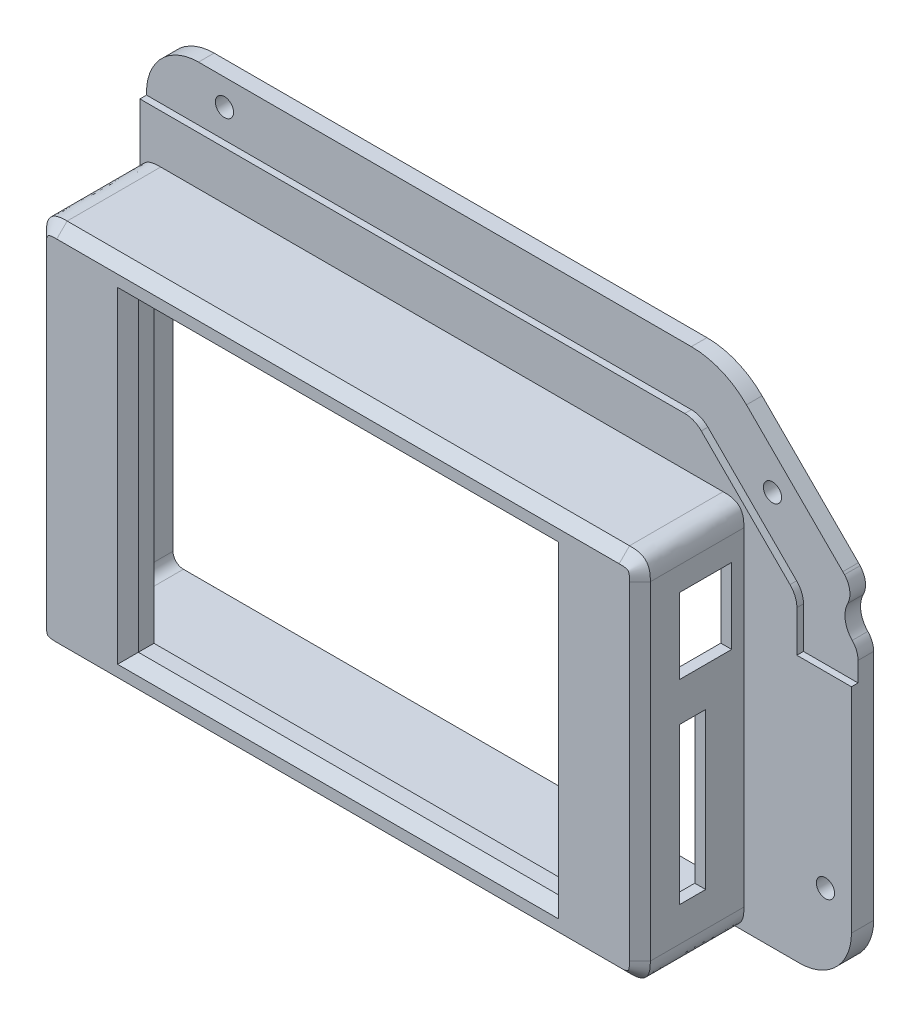
SolidWorks part; units mm, degrees
material "ABS"
ref_plane "Front Plane" through (0, 0, 0) normal (0, 0, 1) x (1, 0, 0)
ref_plane "Top Plane" through (0, 0, 0) normal (0, 1, 0) x (1, 0, 0)
ref_plane "Right Plane" through (0, 0, 0) normal (1, 0, 0) x (0, 0, -1)
sketch "Sketch1" plane through (0, 0, 0) normal (0, 0, 1) x (1, 0, 0)
  line L0 (56, 25) -> (58.1, 25)
  line L1 (58.1, 25) -> (58.1, -5)
  line L2 (58.1, -5) -> (56, -5)
  line L3 (56, -5) -> (56, 25)
  line L4 (56, -12.5) -> (58.1, -12.5)
  line L5 (58.1, -12.5) -> (58.1, -27)
  line L6 (58.1, -27) -> (56, -27)
  line L7 (56, -27) -> (56, -12.5)
  line L8 (47.6, -33.5) -> (54, -33.5)
  line L9 (56, -31.5) -> (56, -25.1)
  line L10 (56, -25.1) -> (51, -25.1)
  line L11 (47.6, -28.5) -> (47.6, -33.5)
  line L12 (56, 25.1) -> (56, 31.5)
  line L13 (54, 33.5) -> (47.6, 33.5)
  line L14 (47.6, 33.5) -> (47.6, 28.5)
  line L15 (51, 25.1) -> (56, 25.1)
  line L16 (-47.6, 33.5) -> (-54, 33.5)
  line L17 (-56, 31.5) -> (-56, 25.1)
  line L18 (-56, 25.1) -> (-51, 25.1)
  line L19 (-47.6, 28.5) -> (-47.6, 33.5)
  line L20 (-56, -25.1) -> (-56, -31.5)
  line L21 (-54, -33.5) -> (-47.6, -33.5)
  line L22 (-47.6, -33.5) -> (-47.6, -28.5)
  line L23 (-51, -25.1) -> (-56, -25.1)
  line L24 (58.1, -31.6) -> (58.1, 31.6)
  line L25 (54.1, 35.6) -> (-54.1, 35.6)
  line L26 (-58.1, 31.6) -> (-58.1, -31.6)
  line L27 (-54.1, -35.6) -> (54.1, -35.6)
  line L28 (42.5, -31.5) -> (42.5, 31.5)
  line L29 (42.5, 31.5) -> (-42.5, 31.5)
  line L30 (-42.5, 31.5) -> (-42.5, -31.5)
  line L31 (-42.5, -31.5) -> (42.5, -31.5)
  line L32 (40.4, 29.4) -> (-40.4, 29.4)
  line L33 (-40.4, 29.4) -> (-40.4, -29.4)
  line L34 (-40.4, -29.4) -> (40.4, -29.4)
  line L35 (40.4, -29.4) -> (40.4, 29.4)
  line L36 (-40.4, 0) -> (40.4, 0) construction
  line L37 (0, 29.4) -> (0, -29.4) construction
  line L38 (47.6, 33.5) -> (-47.6, 33.5)
  line L39 (-56, 25.1) -> (-56, -25.1)
  line L40 (-47.6, -33.5) -> (47.6, -33.5)
  line L41 (56, -12.5) -> (56, -5)
  arc A0 (54, -33.5) -> (56, -31.5) centre (54, -31.5) ccw
  arc A1 (51, -25.1) -> (47.6, -28.5) centre (51, -28.5) ccw
  arc A2 (56, 31.5) -> (54, 33.5) centre (54, 31.5) ccw
  arc A3 (47.6, 28.5) -> (51, 25.1) centre (51, 28.5) ccw
  arc A4 (-54, 33.5) -> (-56, 31.5) centre (-54, 31.5) ccw
  arc A5 (-51, 25.1) -> (-47.6, 28.5) centre (-51, 28.5) ccw
  arc A6 (-56, -31.5) -> (-54, -33.5) centre (-54, -31.5) ccw
  arc A7 (-47.6, -28.5) -> (-51, -25.1) centre (-51, -28.5) ccw
  circle A8 centre (51, 28.5) radius 1.3
  circle A9 centre (-51, 28.5) radius 1.3
  circle A10 centre (-51, -28.5) radius 1.3
  circle A11 centre (51, -28.5) radius 1.3
  spline S0 degree 5 poles (54.1, -35.6) (54.7728, -35.6) (55.4456, -35.6) (56.9284, -35.3132) (57.8132, -34.4284) (58.1, -32.9456) (58.1, -32.2728) (58.1, -31.6) knots 0 0 0 0 0 0 0.5 0.5 1 1 1 1 1 1
  spline S1 degree 5 poles (58.1, 31.6) (58.1, 32.2728) (58.1, 32.9456) (57.8132, 34.4284) (56.9284, 35.3132) (55.4456, 35.6) (54.7728, 35.6) (54.1, 35.6) knots 0 0 0 0 0 0 0.5 0.5 1 1 1 1 1 1
  spline S2 degree 5 poles (-54.1, 35.6) (-54.7728, 35.6) (-55.4456, 35.6) (-56.9284, 35.3132) (-57.8132, 34.4284) (-58.1, 32.9456) (-58.1, 32.2728) (-58.1, 31.6) knots 0 0 0 0 0 0 0.5 0.5 1 1 1 1 1 1
  spline S3 degree 5 poles (-58.1, -31.6) (-58.1, -32.2728) (-58.1, -32.9456) (-57.8132, -34.4284) (-56.9284, -35.3132) (-55.4456, -35.6) (-54.7728, -35.6) (-54.1, -35.6) knots 0 0 0 0 0 0 0.5 0.5 1 1 1 1 1 1
sketch "Sketch2" plane through (0, 0, 0) normal (0, 0, 1) x (1, 0, 0)
  line L0 (98.7914, 85.4501) -> (98.7914, -409.5499)
  line L1 (95.3675, 85.4501) -> (95.3675, -409.5499)
  line L2 (-376.1657, 85.4501) -> (93.7486, 85.4501)
  line L3 (-376.1657, 82.0262) -> (93.7486, 82.0262)
  line L4 (95.3675, 85.4501) -> (73.7914, 85.4501)
  line L5 (-329.1375, 45.4501) -> (46.7203, 45.4501)
  line L6 (50.2559, 43.9857) -> (67.3269, 26.9146)
  line L7 (68.7914, 80.4501) -> (68.7914, -404.5499)
  arc A0 (73.7914, 85.4501) -> (68.7914, 80.4501) centre (73.7914, 80.4501) ccw
  circle A1 centre (61.1725, 65.1501) radius 2.75
  circle A2 centre (81.27, 75.4501) radius 2.5
  circle A3 centre (81.27, 50.4501) radius 2.5
  circle A4 centre (81.27, 25.4501) radius 2.5
  arc A5 (50.2559, 43.9857) -> (46.7203, 45.4501) centre (46.7203, 40.4501) ccw
  arc A6 (68.7914, 23.3791) -> (67.3269, 26.9146) centre (63.7914, 23.3791) ccw
sketch "Sketch3" plane through (0, 0, 0) normal (0, 0, 1) x (1, 0, 0)
  line L0 (-47.6, -33.5) -> (47.6, -33.5) construction
  line L1 (-56, -25.1) -> (-56, -31.5) construction
  line L2 (-56, 25.1) -> (-56, -25.1) construction
  line L3 (-58.1, 31.6) -> (-58.1, -31.6) construction
  line L4 (-54.1, -35.6) -> (54.1, -35.6) construction
  line L5 (-47.6, -33.5) -> (54, -33.5)
  line L6 (-56, -25.1) -> (-56, -31.5)
  line L7 (-56, 31.5) -> (-56, -25.1)
  line L8 (-58.1, 45.4501) -> (-58.1, -31.6)
  line L9 (-54.1, -35.6) -> (68.7914, -35.6)
  line L12 (78.7914, 80.4501) -> (78.7914, -404.5499)
  line L13 (78.7914, 25.4501) -> (78.7914, -25.6)
  line L16 (78.7914, 15.4501) -> (58.1, 15.4501) construction
  line L17 (58.1, 25) -> (58.1, -5) construction
  line L18 (57.3269, 51.0567) -> (74.398, 33.9857)
  line L19 (-329.1375, 55.4501) -> (46.7203, 55.4501)
  line L20 (57.3269, 51.0567) -> (75.8625, 32.5212)
  line L21 (-48.1, 55.4501) -> (46.7203, 55.4501)
  line L22 (-376.1657, 85.4501) -> (93.7486, 85.4501) construction
  line L23 (78.7914, 14.9501) -> (58.1, 14.9501)
  line L28 (56, -31.5) -> (56, -25.1) construction
  line L29 (56, -27) -> (56, -12.5) construction
  line L30 (56, -12.5) -> (56, -5) construction
  line L31 (56, -5) -> (56, 25) construction
  line L32 (56, 25.1) -> (56, 31.5) construction
  line L33 (54, 33.5) -> (47.6, 33.5) construction
  line L34 (47.6, 33.5) -> (-47.6, 33.5) construction
  line L35 (-47.6, 33.5) -> (-54, 33.5) construction
  line L36 (56, -31.5) -> (56, -25.1)
  line L37 (56, -27) -> (56, -12.5)
  line L38 (56, -12.5) -> (56, -5)
  line L39 (56, -5) -> (56, 25)
  line L40 (56, 25.1) -> (56, 31.5)
  line L41 (54, 33.5) -> (47.6, 33.5)
  line L42 (47.6, 33.5) -> (-47.6, 33.5)
  line L43 (-47.6, 33.5) -> (-54, 33.5)
  line L44 (58.1, -31.6) -> (58.1, 31.6) construction
  line L45 (54.1, 35.6) -> (-54.1, 35.6) construction
  line L46 (58.1, -31.6) -> (58.1, 31.6)
  line L47 (54.1, 35.6) -> (-54.1, 35.6)
  arc A0 (-56, -31.5) -> (-54, -33.5) centre (-54, -31.5) ccw construction
  arc A1 (-56, -31.5) -> (-54, -33.5) centre (-54, -31.5) ccw
  arc A2 (68.7914, -35.6) -> (78.7914, -25.6) centre (68.7914, -25.6) ccw
  arc A5 (57.3269, 51.0567) -> (46.7203, 55.4501) centre (46.7203, 40.4501) ccw
  arc A6 (57.3269, 51.0567) -> (46.7203, 55.4501) centre (46.7203, 40.4501) ccw
  arc A8 (75.8625, 32.5212) -> (78.7914, 25.4501) centre (68.7914, 25.4501) cw
  arc A9 (54, -33.5) -> (56, -31.5) centre (54, -31.5) ccw construction
  arc A10 (56, 31.5) -> (54, 33.5) centre (54, 31.5) ccw construction
  arc A11 (-54, 33.5) -> (-56, 31.5) centre (-54, 31.5) ccw construction
  arc A12 (54, -33.5) -> (56, -31.5) centre (54, -31.5) ccw
  arc A13 (56, 31.5) -> (54, 33.5) centre (54, 31.5) ccw
  arc A14 (-54, 33.5) -> (-56, 31.5) centre (-54, 31.5) ccw
  arc A15 (-58.1, 45.4501) -> (-48.1, 55.4501) centre (-48.1, 45.4501) cw
  spline S0 degree 5 poles (-451.1974, 887.8948) (-47.5589, -137.72) (-52.7107, -16.9947) (-63.1302, -36.2248) (-58.7249, -40.6302) (-39.4949, -30.2108) (-160.2167, -25.059) (865.3606, -428.6839) knots -1.989435 -1.989435 -1.989435 -1.989435 -1.989435 -1.989435 0.5 0.5 2.989419 2.989419 2.989419 2.989419 2.989419 2.989419 only from (-58.1, -31.6) to (-54.1, -35.6) construction
  spline S1 degree 5 poles (-58.1, -31.6) (-58.1, -32.2728) (-58.1, -32.9456) (-57.8132, -34.4284) (-56.9284, -35.3132) (-55.4456, -35.6) (-54.7728, -35.6) (-54.1, -35.6) knots 0 0 0 0 0 0 0.5 0.5 1 1 1 1 1 1
  spline S2 degree 5 poles (-865.3948, -428.6974) (160.22, -25.0589) (39.4947, -30.2107) (58.7248, -40.6302) (63.1302, -36.2249) (52.7108, -16.9949) (47.559, -137.7167) (451.1839, 887.8606) knots -1.989435 -1.989435 -1.989435 -1.989435 -1.989435 -1.989435 0.5 0.5 2.989419 2.989419 2.989419 2.989419 2.989419 2.989419 only from (54.1, -35.6) to (58.1, -31.6) construction
  spline S3 degree 5 poles (451.1974, -887.8948) (47.5589, 137.72) (52.7107, 16.9947) (63.1302, 36.2248) (58.7249, 40.6302) (39.4949, 30.2108) (160.2167, 25.059) (-865.3606, 428.6839) knots -1.989435 -1.989435 -1.989435 -1.989435 -1.989435 -1.989435 0.5 0.5 2.989419 2.989419 2.989419 2.989419 2.989419 2.989419 only from (58.1, 31.6) to (54.1, 35.6) construction
  spline S4 degree 5 poles (865.3948, 428.6974) (-160.22, 25.0589) (-39.4947, 30.2107) (-58.7248, 40.6302) (-63.1302, 36.2249) (-52.7108, 16.9949) (-47.559, 137.7167) (-451.1839, -887.8606) knots -1.989435 -1.989435 -1.989435 -1.989435 -1.989435 -1.989435 0.5 0.5 2.989419 2.989419 2.989419 2.989419 2.989419 2.989419 only from (-54.1, 35.6) to (-58.1, 31.6) construction
  spline S5 degree 5 poles (54.1, -35.6) (54.7728, -35.6) (55.4456, -35.6) (56.9284, -35.3132) (57.8132, -34.4284) (58.1, -32.9456) (58.1, -32.2728) (58.1, -31.6) knots 0 0 0 0 0 0 0.5 0.5 1 1 1 1 1 1
  spline S6 degree 5 poles (58.1, 31.6) (58.1, 32.2728) (58.1, 32.9456) (57.8132, 34.4284) (56.9284, 35.3132) (55.4456, 35.6) (54.7728, 35.6) (54.1, 35.6) knots 0 0 0 0 0 0 0.5 0.5 1 1 1 1 1 1
  spline S7 degree 5 poles (-54.1, 35.6) (-54.7728, 35.6) (-55.4456, 35.6) (-56.9284, 35.3132) (-57.8132, 34.4284) (-58.1, 32.9456) (-58.1, 32.2728) (-58.1, 31.6) knots 0 0 0 0 0 0 0.5 0.5 1 1 1 1 1 1
  dimension "D5" = 10
  dimension "D6" = 10
  dimension "D7" = 10
  dimension "D3" = 70
  dimension "D1" = 10
  dimension "D2" = 10
  dimension "D4" = 0.5
extrude "Boss-Extrude1" add sketch "Sketch3" against normal blind 4.27 contours L21 A6 L20 A8 L13 A2 L9 S1 L8 A15
extrude "Cut-Extrude1" cut sketch "Sketch3<4>" against normal blind 1.27 contours L16 L13 A8 L20 A6 L21 A15 L8 S7 L47 S6 L46 region at (12.237, 42.2848, 0)
sketch "Sketch3<4>" plane through (0, 0, 0) normal (0, 0, 1) x (1, 0, 0) same geometry as "Sketch3"
sketch "Sketch4" plane through (0, 0, 0) normal (0, 0, 1) x (1, 0, 0)
  line L0 (-56, -31.5) -> (-56, 31.5)
  line L1 (-54, 33.5) -> (54, 33.5)
  line L2 (56, 31.5) -> (56, -31.5)
  line L3 (54, -33.5) -> (-54, -33.5)
  arc A0 (-56, -31.5) -> (-54, -33.5) centre (-54, -31.5) ccw construction
  arc A1 (54, -33.5) -> (56, -31.5) centre (54, -31.5) ccw construction
  arc A2 (56, 31.5) -> (54, 33.5) centre (54, 31.5) ccw construction
  arc A3 (-54, 33.5) -> (-56, 31.5) centre (-54, 31.5) ccw construction
  arc A4 (-56, -31.5) -> (-54, -33.5) centre (-54, -31.5) ccw
  arc A5 (54, -33.5) -> (56, -31.5) centre (54, -31.5) ccw
  arc A6 (56, 31.5) -> (54, 33.5) centre (54, 31.5) ccw
  arc A7 (-54, 33.5) -> (-56, 31.5) centre (-54, 31.5) ccw
extrude "Cut-Extrude2" cut sketch "Sketch4" against normal through all
sketch "Sketch5" plane through (0, 0, 0) normal (0, 0, 1) x (1, 0, 0)
  line L0 (54.1, -35.6) -> (-54.1, -35.6)
  line L1 (-58.1, -31.6) -> (-58.1, 31.6)
  line L2 (-54.1, 35.6) -> (54.1, 35.6)
  line L3 (58.1, 31.6) -> (58.1, -31.6)
  line L4 (56, -31.5) -> (56, 31.5) construction
  line L5 (-54, -33.5) -> (54, -33.5) construction
  line L6 (-56, 31.5) -> (-56, -31.5) construction
  line L7 (54, 33.5) -> (-54, 33.5) construction
  line L8 (56, -31.5) -> (56, 31.5)
  line L9 (-54, -33.5) -> (54, -33.5)
  line L10 (-56, 31.5) -> (-56, -31.5)
  line L11 (54, 33.5) -> (-54, 33.5)
  arc A0 (56, 31.5) -> (54, 33.5) centre (54, 31.5) ccw construction
  arc A1 (54, -33.5) -> (56, -31.5) centre (54, -31.5) ccw construction
  arc A2 (-56, -31.5) -> (-54, -33.5) centre (-54, -31.5) ccw construction
  arc A3 (-54, 33.5) -> (-56, 31.5) centre (-54, 31.5) ccw construction
  arc A4 (56, 31.5) -> (54, 33.5) centre (54, 31.5) ccw
  arc A5 (54, -33.5) -> (56, -31.5) centre (54, -31.5) ccw
  arc A6 (-56, -31.5) -> (-54, -33.5) centre (-54, -31.5) ccw
  arc A7 (-54, 33.5) -> (-56, 31.5) centre (-54, 31.5) ccw
  spline S0 degree 5 poles (-1799.305, -785.9818) (240.9375, -22.324) (35.4019, -27.9004) (59.4949, -41.9944) (64.4944, -36.995) (50.4005, -12.9021) (44.8241, -218.4331) (808.4613, 1821.7503) knots -2.325198 -2.325198 -2.325198 -2.325198 -2.325198 -2.325198 0.5 0.5 3.325183 3.325183 3.325183 3.325183 3.325183 3.325183 only from (54.1, -35.6) to (58.1, -31.6) construction
  spline S1 degree 5 poles (-808.4818, 1821.805) (-44.824, -218.4375) (-50.4004, -12.9019) (-64.4944, -36.9949) (-59.495, -41.9944) (-35.4021, -27.9005) (-240.9331, -22.3241) (1799.2503, -785.9613) knots -2.325198 -2.325198 -2.325198 -2.325198 -2.325198 -2.325198 0.5 0.5 3.325183 3.325183 3.325183 3.325183 3.325183 3.325183 only from (-58.1, -31.6) to (-54.1, -35.6) construction
  spline S2 degree 5 poles (1799.305, 785.9818) (-240.9375, 22.324) (-35.4019, 27.9004) (-59.4949, 41.9944) (-64.4944, 36.995) (-50.4005, 12.9021) (-44.8241, 218.4331) (-808.4613, -1821.7503) knots -2.325198 -2.325198 -2.325198 -2.325198 -2.325198 -2.325198 0.5 0.5 3.325183 3.325183 3.325183 3.325183 3.325183 3.325183 only from (-54.1, 35.6) to (-58.1, 31.6) construction
  spline S3 degree 5 poles (808.4818, -1821.805) (44.824, 218.4375) (50.4004, 12.9019) (64.4944, 36.9949) (59.495, 41.9944) (35.4021, 27.9005) (240.9331, 22.3241) (-1799.2503, 785.9613) knots -2.325198 -2.325198 -2.325198 -2.325198 -2.325198 -2.325198 0.5 0.5 3.325183 3.325183 3.325183 3.325183 3.325183 3.325183 only from (58.1, 31.6) to (54.1, 35.6) construction
  spline S4 degree 5 poles (54.1, -35.6) (54.7728, -35.6) (55.4456, -35.6) (56.9284, -35.3132) (57.8132, -34.4284) (58.1, -32.9456) (58.1, -32.2728) (58.1, -31.6) knots 0 0 0 0 0 0 0.5 0.5 1 1 1 1 1 1
  spline S5 degree 5 poles (-58.1, -31.6) (-58.1, -32.2728) (-58.1, -32.9456) (-57.8132, -34.4284) (-56.9284, -35.3132) (-55.4456, -35.6) (-54.7728, -35.6) (-54.1, -35.6) knots 0 0 0 0 0 0 0.5 0.5 1 1 1 1 1 1
  spline S6 degree 5 poles (-54.1, 35.6) (-54.7728, 35.6) (-55.4456, 35.6) (-56.9284, 35.3132) (-57.8132, 34.4284) (-58.1, 32.9456) (-58.1, 32.2728) (-58.1, 31.6) knots 0 0 0 0 0 0 0.5 0.5 1 1 1 1 1 1
  spline S7 degree 5 poles (58.1, 31.6) (58.1, 32.2728) (58.1, 32.9456) (57.8132, 34.4284) (56.9284, 35.3132) (55.4456, 35.6) (54.7728, 35.6) (54.1, 35.6) knots 0 0 0 0 0 0 0.5 0.5 1 1 1 1 1 1
extrude "Boss-Extrude2" add sketch "Sketch5" along normal blind 18
sketch "Sketch6" plane through (0, 0, 18) normal (0, 0, 1) x (1, 0, 0)
  line L0 (-40.4, 29.4) -> (-40.4, -29.4) construction
  line L1 (-40.4, -29.4) -> (40.4, -29.4) construction
  line L2 (40.4, -29.4) -> (40.4, 29.4) construction
  line L3 (40.4, 29.4) -> (-40.4, 29.4) construction
  line L4 (58.1, -31.6) -> (58.1, 31.6)
  line L5 (54.1, 35.6) -> (-54.1, 35.6)
  line L6 (-58.1, 31.6) -> (-58.1, -31.6)
  line L7 (-54.1, -35.6) -> (54.1, -35.6)
  line L8 (58.1, -31.6) -> (58.1, 31.6)
  line L9 (54.1, 35.6) -> (-54.1, 35.6)
  line L10 (-58.1, 31.6) -> (-58.1, -31.6)
  line L11 (-54.1, -35.6) -> (54.1, -35.6)
  line L12 (-40.4, 29.4) -> (-40.4, -29.4)
  line L13 (-40.4, -29.4) -> (40.4, -29.4)
  line L14 (40.4, -29.4) -> (40.4, 29.4)
  line L15 (40.4, 29.4) -> (-40.4, 29.4)
  spline S4 degree 5 poles (-2737.4679, -1132.0779) (312.9698, -20.6591) (32.5131, -26.1748) (60.0701, -42.9574) (65.4574, -37.5702) (48.6749, -10.0133) (43.1592, -290.4662) (1154.5598, 2759.9182) knots -2.544295 -2.544295 -2.544295 -2.544295 -2.544295 -2.544295 0.5 0.5 3.544285 3.544285 3.544285 3.544285 3.544285 3.544285 only from (54.1, -35.6) to (58.1, -31.6)
  spline S5 degree 5 poles (1154.5779, -2759.9679) (43.1591, 290.4698) (48.6748, 10.0131) (65.4574, 37.5701) (60.0702, 42.9574) (32.5133, 26.1749) (312.9662, 20.6592) (-2737.4182, 1132.0598) knots -2.544295 -2.544295 -2.544295 -2.544295 -2.544295 -2.544295 0.5 0.5 3.544285 3.544285 3.544285 3.544285 3.544285 3.544285 only from (58.1, 31.6) to (54.1, 35.6)
  spline S6 degree 5 poles (2737.4679, 1132.0779) (-312.9698, 20.6591) (-32.5131, 26.1748) (-60.0701, 42.9574) (-65.4574, 37.5702) (-48.6749, 10.0133) (-43.1592, 290.4662) (-1154.5598, -2759.9182) knots -2.544295 -2.544295 -2.544295 -2.544295 -2.544295 -2.544295 0.5 0.5 3.544285 3.544285 3.544285 3.544285 3.544285 3.544285 only from (-54.1, 35.6) to (-58.1, 31.6)
  spline S7 degree 5 poles (-1154.5779, 2759.9679) (-43.1591, -290.4698) (-48.6748, -10.0131) (-65.4574, -37.5701) (-60.0702, -42.9574) (-32.5133, -26.1749) (-312.9662, -20.6592) (2737.4182, -1132.0598) knots -2.544295 -2.544295 -2.544295 -2.544295 -2.544295 -2.544295 0.5 0.5 3.544285 3.544285 3.544285 3.544285 3.544285 3.544285 only from (-58.1, -31.6) to (-54.1, -35.6)
  spline S8 degree 5 poles (54.1, -35.6) (54.7728, -35.6) (55.4456, -35.6) (56.9284, -35.3132) (57.8132, -34.4284) (58.1, -32.9456) (58.1, -32.2728) (58.1, -31.6) knots 0 0 0 0 0 0 0.5 0.5 1 1 1 1 1 1
  spline S9 degree 5 poles (58.1, 31.6) (58.1, 32.2728) (58.1, 32.9456) (57.8132, 34.4284) (56.9284, 35.3132) (55.4456, 35.6) (54.7728, 35.6) (54.1, 35.6) knots 0 0 0 0 0 0 0.5 0.5 1 1 1 1 1 1
  spline S10 degree 5 poles (-54.1, 35.6) (-54.7728, 35.6) (-55.4456, 35.6) (-56.9284, 35.3132) (-57.8132, 34.4284) (-58.1, 32.9456) (-58.1, 32.2728) (-58.1, 31.6) knots 0 0 0 0 0 0 0.5 0.5 1 1 1 1 1 1
  spline S11 degree 5 poles (-58.1, -31.6) (-58.1, -32.2728) (-58.1, -32.9456) (-57.8132, -34.4284) (-56.9284, -35.3132) (-55.4456, -35.6) (-54.7728, -35.6) (-54.1, -35.6) knots 0 0 0 0 0 0 0.5 0.5 1 1 1 1 1 1
  dimension "D1" = 0
extrude "Boss-Extrude3" add sketch "Sketch6" along normal blind 2
sketch "Sketch7" plane through (0, 0, 18) normal (0, 0, -1) x (-1, 0, 0)
  line L0 (-47.6, -33.5) -> (-54, -33.5) construction
  line L1 (-56, -31.5) -> (-56, -25.1) construction
  line L2 (-56, -25.1) -> (-51, -25.1) construction
  line L3 (-47.6, -28.5) -> (-47.6, -33.5) construction
  line L4 (56, -25.1) -> (56, -31.5) construction
  line L5 (54, -33.5) -> (47.6, -33.5) construction
  line L6 (47.6, -33.5) -> (47.6, -28.5) construction
  line L7 (51, -25.1) -> (56, -25.1) construction
  line L8 (47.6, 33.5) -> (54, 33.5) construction
  line L9 (56, 31.5) -> (56, 25.1) construction
  line L10 (56, 25.1) -> (51, 25.1) construction
  line L11 (47.6, 28.5) -> (47.6, 33.5) construction
  line L12 (-47.6, 33.5) -> (-47.6, 28.5) construction
  line L13 (-51, 25.1) -> (-56, 25.1) construction
  line L14 (-56, 25.1) -> (-56, 31.5) construction
  line L15 (-54, 33.5) -> (-47.6, 33.5) construction
  line L16 (-47.6, -33.5) -> (-54, -33.5)
  line L17 (-56, -31.5) -> (-56, -25.1)
  line L18 (-56, -25.1) -> (-51, -25.1)
  line L19 (-47.6, -28.5) -> (-47.6, -33.5)
  line L20 (56, -25.1) -> (56, -31.5)
  line L21 (54, -33.5) -> (47.6, -33.5)
  line L22 (47.6, -33.5) -> (47.6, -28.5)
  line L23 (51, -25.1) -> (56, -25.1)
  line L24 (47.6, 33.5) -> (54, 33.5)
  line L25 (56, 31.5) -> (56, 25.1)
  line L26 (56, 25.1) -> (51, 25.1)
  line L27 (47.6, 28.5) -> (47.6, 33.5)
  line L28 (-47.6, 33.5) -> (-47.6, 28.5)
  line L29 (-51, 25.1) -> (-56, 25.1)
  line L30 (-56, 25.1) -> (-56, 31.5)
  line L31 (-54, 33.5) -> (-47.6, 33.5)
  circle A0 centre (-51, -28.5) radius 1.3 construction
  circle A1 centre (51, -28.5) radius 1.3 construction
  circle A2 centre (51, 28.5) radius 1.3 construction
  circle A3 centre (-51, 28.5) radius 1.3 construction
  arc A4 (-47.6, -28.5) -> (-51, -25.1) centre (-51, -28.5) ccw construction
  arc A5 (-56, -31.5) -> (-54, -33.5) centre (-54, -31.5) ccw construction
  arc A6 (54, -33.5) -> (56, -31.5) centre (54, -31.5) ccw construction
  arc A7 (51, -25.1) -> (47.6, -28.5) centre (51, -28.5) ccw construction
  arc A8 (56, 31.5) -> (54, 33.5) centre (54, 31.5) ccw construction
  arc A9 (47.6, 28.5) -> (51, 25.1) centre (51, 28.5) ccw construction
  arc A10 (-51, 25.1) -> (-47.6, 28.5) centre (-51, 28.5) ccw construction
  arc A11 (-54, 33.5) -> (-56, 31.5) centre (-54, 31.5) ccw construction
  circle A12 centre (-51, -28.5) radius 1.3
  circle A13 centre (51, -28.5) radius 1.3
  circle A14 centre (51, 28.5) radius 1.3
  circle A15 centre (-51, 28.5) radius 1.3
  arc A16 (-47.6, -28.5) -> (-51, -25.1) centre (-51, -28.5) ccw
  arc A17 (-56, -31.5) -> (-54, -33.5) centre (-54, -31.5) ccw
  arc A18 (54, -33.5) -> (56, -31.5) centre (54, -31.5) ccw
  arc A19 (51, -25.1) -> (47.6, -28.5) centre (51, -28.5) ccw
  arc A20 (56, 31.5) -> (54, 33.5) centre (54, 31.5) ccw
  arc A21 (47.6, 28.5) -> (51, 25.1) centre (51, 28.5) ccw
  arc A22 (-51, 25.1) -> (-47.6, 28.5) centre (-51, 28.5) ccw
  arc A23 (-54, 33.5) -> (-56, 31.5) centre (-54, 31.5) ccw
extrude "Boss-Extrude4" add sketch "Sketch7" along normal blind 5
chamfer "Chamfer1" distance 2 angle 45 13 edges at (0, -33.5, 18) (47.6, -31, 18) (53.5, -25.1, 18) (48.5958, -26.0958, 18) (56, 0, 18) (53.5, 25.1, 18) (47.6, 31, 18) (48.5958, 26.0958, 18) (0, 33.5, 18) (-47.6, 31, 18) (-48.5958, 26.0958, 18) (-53.5, 25.1, 18) (-56, 0, 18)
sketch "Sketch8" plane through (0, 0, 18) normal (0, 0, -1) x (-1, 0, 0)
  line L0 (-47.6, 33.5) -> (47.6, 33.5) construction
  line L1 (-42.5, 33.5) -> (42.5, 33.5)
  line L2 (-42.5, 33.5) -> (-42.5, -33.5)
  line L3 (-42.5, -33.5) -> (42.5, -33.5)
  line L4 (42.5, 33.5) -> (42.5, -33.5)
  line L6 (47.6, -33.5) -> (-47.6, -33.5) construction
  line L7 (42.5, 31.5) -> (42.5, -31.5) construction
  line L8 (-42.5, -31.5) -> (-42.5, 31.5) construction
  line L9 (40.4, 29.4) -> (40.4, -29.4) construction
  line L10 (40.4, -29.4) -> (-40.4, -29.4) construction
  line L11 (-40.4, -29.4) -> (-40.4, 29.4) construction
  line L12 (-40.4, 29.4) -> (40.4, 29.4) construction
  line L13 (40.4, 29.4) -> (40.4, -29.4)
  line L14 (40.4, -29.4) -> (-40.4, -29.4)
  line L15 (-40.4, -29.4) -> (-40.4, 29.4)
  line L16 (-40.4, 29.4) -> (40.4, 29.4)
extrude "Boss-Extrude5" add sketch "Sketch8" along normal blind 3
chamfer "Chamfer2" distance 2 angle 45 12 edges at (40.4, 0, 20) (0, -29.4, 20) (-40.4, 0, 20) (0, 29.4, 20) (-57.1039, -34.8309, 20) (0, -35.6, 20) (-58.1, 0, 20) (57.3309, -34.6039, 20) (-57.3309, 34.6039, 20) (58.1, 0, 20) (0, 35.6, 20) (57.1039, 34.8309, 20)
sketch "Sketch9" plane through (56, 0, 0) normal (-1, 0, 0) x (0, 0, 1)
  line L0 (13, -25.1) -> (13, -31.5) construction
  line L1 (12.35, 12.5) -> (2.35, 12.5)
  line L2 (12.35, 12.5) -> (12.35, 27)
  line L3 (12.35, 27) -> (2.35, 27)
  line L4 (2.35, 12.5) -> (2.35, 27)
  line L5 (12.35, -25) -> (7.35, -25)
  line L6 (12.35, -25) -> (12.35, 5)
  line L7 (12.35, 5) -> (7.35, 5)
  line L8 (7.35, -25) -> (7.35, 5)
  line L9 (13, 31.5) -> (13, 25.1) construction
  line L10 (-1.27, 31.6) -> (18, 31.6) construction
  line L12 (18, -31.6) -> (0, -31.6) construction
  dimension "D1" = 10
  dimension "D2" = 0.65
  dimension "D3" = 0.65
  dimension "D4" = 5
  dimension "D5" = 6.6
  dimension "D6" = 30
  dimension "D7" = 14.5
  dimension "D8" = 4.6
extrude "Cut-Extrude3" cut sketch "Sketch9" against normal up to surface (2.1 mm away)
sketch "Sketch10" plane through (0, 0, -4.27) normal (0, 0, -1) x (-1, 0, 0)
  line L10 (-73.7914, 23.3791) -> (-73.7914, -34.2603) construction
  line L11 (48.1, 55.4501) -> (-46.7203, 55.4501) construction
  line L12 (329.1375, 50.4501) -> (-46.7203, 50.4501)
  line L13 (-53.7914, 47.5212) -> (-70.8625, 30.4501)
  line L14 (56.7603, 50.4501) -> (-46.7203, 50.4501) construction
  line L15 (-53.7914, 47.5212) -> (-70.8625, 30.4501) construction
  line L16 (-57.3269, 51.0567) -> (-75.8625, 32.5212) construction
  line L17 (-78.7914, 25.4501) -> (-78.7914, -25.6) construction
  line L18 (54.1, -35.6) -> (-68.7914, -35.6) construction
  line L19 (58.1, 45.4501) -> (58.1, -31.6) construction
  line L20 (48.1, 55.4501) -> (-46.7203, 55.4501)
  line L21 (-57.3269, 51.0567) -> (-75.8625, 32.5212)
  line L22 (-78.7914, 25.4501) -> (-78.7914, -25.6)
  line L23 (54.1, -35.6) -> (-68.7914, -35.6)
  line L24 (58.1, 45.4501) -> (58.1, -31.6)
  arc A8 (-78.7914, -25.6) -> (-68.7914, -35.6) centre (-68.7914, -25.6) ccw construction
  arc A10 (-70.8625, 30.4501) -> (-73.7914, 23.3791) centre (-63.7914, 23.3791) ccw
  arc A11 (-46.7203, 50.4501) -> (-53.7914, 47.5212) centre (-46.7203, 40.4501) ccw
  arc A12 (-70.8625, 30.4501) -> (-73.7914, 23.3791) centre (-63.7914, 23.3791) ccw construction
  arc A13 (-46.7203, 50.4501) -> (-53.7914, 47.5212) centre (-46.7203, 40.4501) ccw construction
  arc A14 (-46.7203, 55.4501) -> (-57.3269, 51.0567) centre (-46.7203, 40.4501) ccw construction
  arc A15 (-75.8625, 32.5212) -> (-78.7914, 25.4501) centre (-68.7914, 25.4501) ccw construction
  arc A16 (58.1, 45.4501) -> (48.1, 55.4501) centre (48.1, 45.4501) ccw construction
  arc A17 (-46.7203, 55.4501) -> (-57.3269, 51.0567) centre (-46.7203, 40.4501) ccw
  arc A18 (-75.8625, 32.5212) -> (-78.7914, 25.4501) centre (-68.7914, 25.4501) ccw
  arc A19 (-78.7914, -25.6) -> (-68.7914, -35.6) centre (-68.7914, -25.6) ccw
  circle A20 centre (43.1, 50.4501) radius 1.75
  circle A21 centre (-62.3269, 38.9857) radius 1.75
  circle A22 centre (-73.7914, -20.6) radius 1.75
  circle A23 centre (-81.27, 25.4501) radius 5
  spline S0 degree 5 poles (451.1974, 887.8948) (47.5589, -137.72) (52.7107, -16.9947) (63.1302, -36.2248) (58.7249, -40.6302) (39.4949, -30.2108) (160.2167, -25.059) (-865.3606, -428.6839) knots -1.989435 -1.989435 -1.989435 -1.989435 -1.989435 -1.989435 0.5 0.5 2.989419 2.989419 2.989419 2.989419 2.989419 2.989419 only from (58.1, -31.6) to (54.1, -35.6) construction
  spline S1 degree 5 poles (58.1, -31.6) (58.1, -32.2728) (58.1, -32.9456) (57.8132, -34.4284) (56.9284, -35.3132) (55.4456, -35.6) (54.7728, -35.6) (54.1, -35.6) knots 0 0 0 0 0 0 0.5 0.5 1 1 1 1 1 1
  line M18 (-78.7914, 25.4501) -> (-78.7914, -25.6)
  dimension "D2" = 3.5
  dimension "D3" = 5
  dimension "D4" = 5
  dimension "D5" = 10
  dimension "D1" = 5
extrude "Cut-Extrude4" cut sketch "Sketch10" against normal up to next contours A18 A23 M18 | A23 A18 M18 | A22 | A21 | A20 region at (77.6926, 25.2025, -4.27) region at (82.0719, 25.5057, -4.27)
fillet "Fillet1" radius 4 2 edges at (78.0358, 29.2633, -2.77) (78.7914, 21.1077, -2.77)
sketch "Sketch12" plane through (0, 0, -1.27) normal (0, 0, 1) x (1, 0, 0)
  line L0 (54.1, 35.6) -> (-54.1, 35.6) construction
  line L1 (58.1, 15.4501) -> (58.1, 31.6) construction
  line L2 (78.7914, 15.4501) -> (58.1, 15.4501) construction
  line L3 (54.1, 35.6) -> (-54.1, 35.6)
  line L4 (58.1, 15.4501) -> (58.1, 31.6)
  line L5 (68.2914, 15.4501) -> (58.1, 15.4501)
  line L6 (-58.1, 45.4501) -> (-58.1, 31.6) construction
  line L7 (-58.1, 44.9501) -> (-58.1, 31.6)
  line L12 (68.2914, 23.3791) -> (68.2914, 15.4501)
  line L14 (66.9734, 26.561) -> (49.9023, 43.6321)
  line L15 (46.7203, 44.9501) -> (-329.1375, 44.9501)
  line L16 (66.9734, 26.561) -> (49.9023, 43.6321)
  line L17 (46.7203, 44.9501) -> (-58.1, 44.9501)
  arc A6 (68.2914, 23.3791) -> (66.9734, 26.561) centre (63.7914, 23.3791) ccw
  arc A7 (49.9023, 43.6321) -> (46.7203, 44.9501) centre (46.7203, 40.4501) ccw
  arc A8 (68.2914, 23.3791) -> (66.9734, 26.561) centre (63.7914, 23.3791) ccw
  arc A9 (49.9023, 43.6321) -> (46.7203, 44.9501) centre (46.7203, 40.4501) ccw
  spline S0 degree 5 poles (2737.4679, 1132.0779) (-312.9698, 20.6591) (-32.5131, 26.1748) (-60.0701, 42.9574) (-65.4574, 37.5702) (-48.6749, 10.0133) (-43.1592, 290.4662) (-1154.5598, -2759.9182) knots -2.544295 -2.544295 -2.544295 -2.544295 -2.544295 -2.544295 0.5 0.5 3.544285 3.544285 3.544285 3.544285 3.544285 3.544285 only from (-54.1, 35.6) to (-58.1, 31.6) construction
  spline S1 degree 5 poles (1154.5779, -2759.9679) (43.1591, 290.4698) (48.6748, 10.0131) (65.4574, 37.5701) (60.0702, 42.9574) (32.5133, 26.1749) (312.9662, 20.6592) (-2737.4182, 1132.0598) knots -2.544295 -2.544295 -2.544295 -2.544295 -2.544295 -2.544295 0.5 0.5 3.544285 3.544285 3.544285 3.544285 3.544285 3.544285 only from (58.1, 31.6) to (54.1, 35.6) construction
  spline S2 degree 5 poles (-54.1, 35.6) (-54.7728, 35.6) (-55.4456, 35.6) (-56.9284, 35.3132) (-57.8132, 34.4284) (-58.1, 32.9456) (-58.1, 32.2728) (-58.1, 31.6) knots 0 0 0 0 0 0 0.5 0.5 1 1 1 1 1 1
  spline S3 degree 5 poles (58.1, 31.6) (58.1, 32.2728) (58.1, 32.9456) (57.8132, 34.4284) (56.9284, 35.3132) (55.4456, 35.6) (54.7728, 35.6) (54.1, 35.6) knots 0 0 0 0 0 0 0.5 0.5 1 1 1 1 1 1
  dimension "D1" = 0.5
extrude "Boss-Extrude7" add sketch "Sketch12" along normal up to surface (1.27 mm away) up to face at (72.0414, -20.6, 0)
